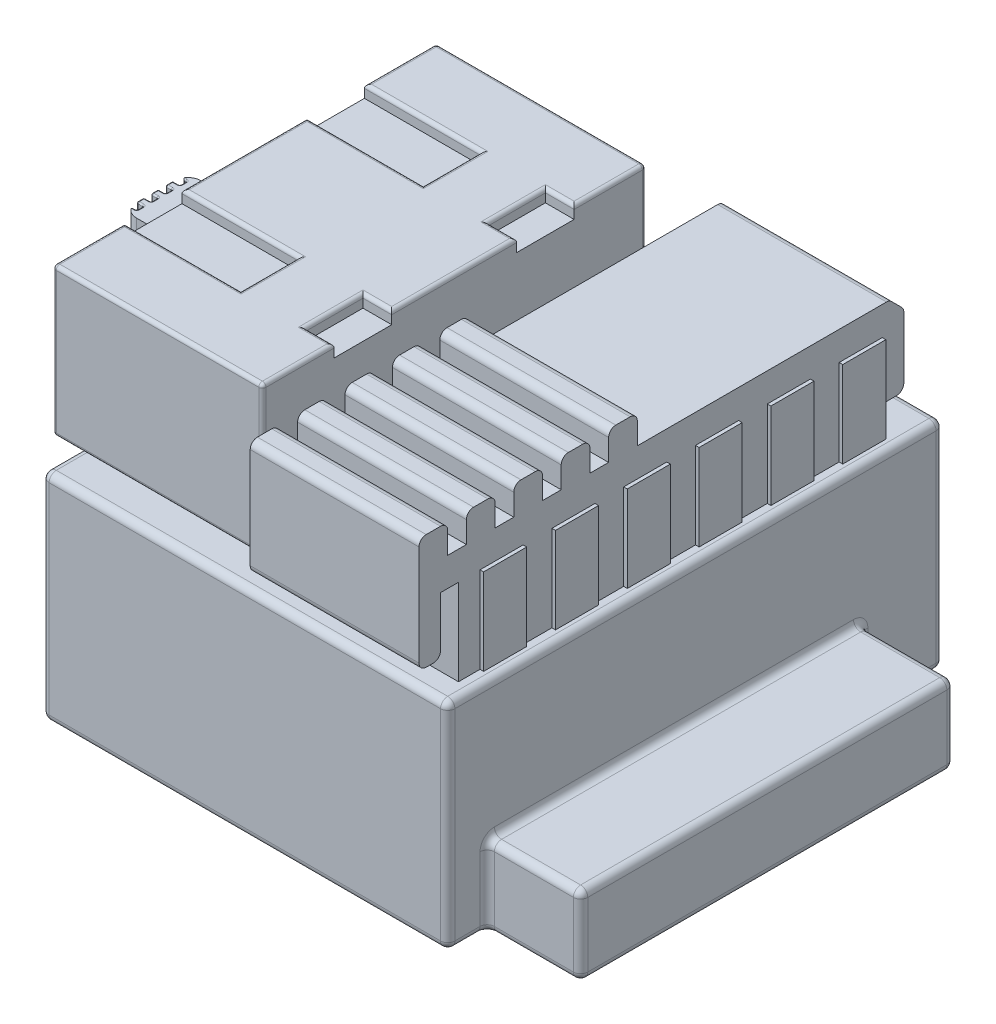
SolidWorks part; units mm, degrees
ref_plane "Front Plane" through (0, 0, 0) normal (0, 0, 1) x (1, 0, 0)
ref_plane "Top Plane" through (0, 0, 0) normal (0, 1, 0) x (1, 0, 0)
ref_plane "Right Plane" through (0, 0, 0) normal (1, 0, 0) x (0, 0, -1)
sketch "Sketch1" plane through (0, 0, 0) normal (0, 1, 0) x (1, 0, 0)
  line L1 (-14.125, -17.25) -> (14.125, -17.25)
  line L2 (-14.125, -17.25) -> (-14.125, 17.25)
  line L3 (-14.125, 17.25) -> (14.125, 17.25)
  line L4 (14.125, -17.25) -> (14.125, 17.25)
  line L5 (-14.125, -17.25) -> (14.125, 17.25) construction
  line L6 (-14.125, 17.25) -> (14.125, -17.25) construction
  line L7 (14.125, 11.5) -> (20.625, 11.5)
  line L8 (14.125, 11.5) -> (14.125, -14.5)
  line L9 (14.125, -14.5) -> (20.625, -14.5)
  line L10 (20.625, 11.5) -> (20.625, -14.5)
  point P0 (0, 0)
  dimension "D1" = 34.5
  dimension "D2" = 28.25
  dimension "D3" = 6.5
  dimension "D4" = 26
  dimension "D5" = 2.75
extrude "Boss-Extrude1" add sketch "Sketch1" along normal blind 15 contours L1 L4 L3 L2 region at (0, 0, 0)
extrude "Boss-Extrude2" add sketch "Sketch1<3>" along normal blind 5.5 contours L10 L7 L4 L9 region at (17.375, 0, 1.5)
sketch "Sketch1<3>" plane through (0, 0, 0) normal (0, 1, 0) x (1, 0, 0) same geometry as "Sketch1"
sketch "Sketch2" plane through (0, 15, 0) normal (0, 1, 0) x (1, 0, 0)
  line L0 (-14.125, -17.25) -> (-14.125, 17.25) construction
  line L1 (-12.125, -14.25) -> (-1.625, -14.25)
  line L2 (-12.125, -14.25) -> (-12.125, 10.75)
  line L3 (-12.125, 10.75) -> (-1.625, 10.75)
  line L4 (-1.625, -14.25) -> (-1.625, 10.75)
  line L5 (-14.125, -17.25) -> (14.125, -17.25) construction
  dimension "D1" = 2
  dimension "D2" = 10.5
  dimension "D3" = 25
  dimension "D4" = 3
extrude "Boss-Extrude3" add sketch "Sketch2" along normal blind 1
sketch "Sketch3" plane through (0, 16, 0) normal (0, 1, 0) x (1, 0, 0)
  line L0 (-14.125, -17.25) -> (14.125, -17.25) construction
  line L1 (-14.875, 10.95) -> (-0.275, 10.95)
  line L2 (-14.875, 10.95) -> (-14.875, -15.75)
  line L3 (-14.875, -15.75) -> (-0.275, -15.75)
  line L4 (-0.275, 10.95) -> (-0.275, -15.75)
  line L5 (-14.125, -17.25) -> (-14.125, 17.25) construction
  dimension "D1" = 1.5
  dimension "D2" = 0.75
  dimension "D3" = 14.6
  dimension "D4" = 26.7
extrude "Boss-Extrude4" add sketch "Sketch3" along normal blind 10.3
sketch "Sketch4" plane through (-14.875, 0, 0) normal (-1, 0, 0) x (0, 0, 1)
  line L0 (-10.95, 21.15) -> (15.75, 21.15) construction
  line L1 (-10.95, 26.3) -> (-10.95, 16) construction
  line L2 (15.75, 26.3) -> (15.75, 16) construction
  line L3 (-2.1, 21.15) -> (6.9, 21.15) construction
  line L4 (-2.1, 19.15) -> (6.9, 19.15)
  line L5 (-2.1, 23.15) -> (6.9, 23.15)
  line L6 (-2.1, 19.15) -> (-2.1, 23.15)
  line L7 (6.9, 19.15) -> (6.9, 23.15)
  circle A0 centre (-7.45, 21.15) radius 0.75
  circle A1 centre (12.25, 21.15) radius 0.75
  circle A2 centre (2.4, 21.15) radius 9.85 construction
  dimension "D1" = 1.5
  dimension "D2" = 3.5
  dimension "D3" = 9
  dimension "D4" = 2
  dimension "D5" = 2
extrude "Cut-Extrude1" cut sketch "Sketch4" against normal blind 2
sketch "Sketch5" plane through (-12.875, 0, 0) normal (-1, 0, 0) x (0, 0, 1)
  line L0 (-2.1, 19.15) -> (6.9, 19.15) construction
  line L1 (6.9, 23.15) -> (2.4, 23.15)
  line L2 (6.9, 23.15) -> (6.9, 19.15)
  line L3 (6.9, 19.15) -> (2.4, 19.15)
  line L4 (2.4, 23.15) -> (2.4, 19.15)
extrude "Boss-Extrude5" add sketch "Sketch5" along normal blind 6
fillet "Fillet1" radius 1 2 edges at (-18.875, 21.15, 2.4) (-18.875, 21.15, 6.9)
sketch "Sketch6" plane through (0, 23.15, 0) normal (0, 1, 0) x (1, 0, 0)
  line L0 (-18.375, -2.5383) -> (-18.375, -6.6821) construction
  line L1 (-18.875, -5.9) -> (-18.875, -3.4) construction
  line L2 (-17.875, -2.4) -> (-14.875, -2.4) construction
  line L3 (-19.375, -2.9) -> (-18.375, -2.9)
  line L4 (-19.375, -2.9) -> (-19.375, -3.4)
  line L5 (-19.375, -3.4) -> (-18.375, -3.4)
  line L6 (-18.375, -2.9) -> (-18.375, -3.4)
  line L7 (-19.375, -3.9) -> (-18.375, -3.9)
  line L8 (-19.375, -3.9) -> (-19.375, -4.4)
  line L9 (-19.375, -4.4) -> (-18.375, -4.4)
  line L10 (-18.375, -3.9) -> (-18.375, -4.4)
  line L11 (-19.375, -4.9) -> (-18.375, -4.9)
  line L12 (-19.375, -4.9) -> (-19.375, -5.4)
  line L13 (-19.375, -5.4) -> (-18.375, -5.4)
  line L14 (-18.375, -4.9) -> (-18.375, -5.4)
  line L15 (-19.375, -5.9) -> (-18.375, -5.9)
  line L16 (-19.375, -5.9) -> (-19.375, -6.4)
  line L17 (-19.375, -6.4) -> (-18.375, -6.4)
  line L18 (-18.375, -5.9) -> (-18.375, -6.4)
  line L19 (-17.875, -6.9) -> (-14.875, -6.9) construction
  line L20 (-19.375, -2.9) -> (-19.375, -6.4) construction
  dimension "D1" = 0.5
  dimension "D2" = 0.5
  dimension "D3" = 0.5
  dimension "D4" = 0.5
  dimension "D5" = 0.5
  dimension "D6" = 0.5
  dimension "D7" = 0.5
  dimension "D8" = 0.5
  dimension "D9" = 0.5
  dimension "D10" = 1
extrude "Cut-Extrude2" cut sketch "Sketch6" against normal blind 6
fillet "Fillet4" radius 0.1 46 edges at (-18.625, 19.15, 3.4) (-18.558, 19.15, 2.9) (-18.558, 23.15, 2.9) (-18.625, 23.15, 3.4) (-18.625, 19.15, 4.4) (-18.625, 19.15, 3.9) (-18.625, 23.15, 3.9) (-18.625, 23.15, 4.4) (-18.625, 19.15, 5.4) (-18.625, 19.15, 4.9) (-18.625, 23.15, 4.9) (-18.625, 23.15, 5.4) (-18.558, 19.15, 6.4) (-18.625, 19.15, 5.9) (-18.625, 23.15, 5.9) (-18.558, 23.15, 6.4) (-18.375, 19.15, 3.15) (-18.375, 21.15, 2.9) (-18.375, 23.15, 3.15) (-18.375, 21.15, 3.4) (-18.875, 21.15, 3.4) (-18.875, 23.15, 3.65) (-18.875, 21.15, 3.9) (-18.875, 19.15, 3.65) (-18.375, 19.15, 4.15) (-18.375, 21.15, 3.9) (-18.375, 23.15, 4.15) (-18.375, 21.15, 4.4) (-18.875, 21.15, 4.4) (-18.875, 23.15, 4.65) (-18.875, 21.15, 4.9) (-18.875, 19.15, 4.65) (-18.375, 19.15, 5.15) (-18.375, 21.15, 4.9) (-18.375, 23.15, 5.15) (-18.375, 21.15, 5.4) (-18.875, 21.15, 5.9) (-18.875, 19.15, 5.65) (-18.875, 21.15, 5.4) (-18.875, 23.15, 5.65) (-18.375, 19.15, 6.15) (-18.375, 21.15, 5.9) (-18.375, 23.15, 6.15) (-18.375, 21.15, 6.4) (-18.741, 21.15, 6.4) (-18.741, 21.15, 2.9)
sketch "Sketch7" plane through (0, 26.3, 0) normal (0, 1, 0) x (1, 0, 0)
  line L0 (-14.875, 10.95) -> (-14.875, -15.75) construction
  line L1 (-14.875, 5.95) -> (-6.775, 5.95)
  line L2 (-14.875, 5.95) -> (-14.875, 1.95)
  line L3 (-14.875, 1.95) -> (-6.775, 1.95)
  line L4 (-0.275, 5.95) -> (-0.275, 1.95)
  line L5 (-0.275, -15.75) -> (-0.275, 10.95) construction
  line L6 (-14.875, -15.75) -> (-0.275, -15.75) construction
  line L7 (-14.875, -6.75) -> (-6.775, -6.75)
  line L8 (-14.875, -6.75) -> (-14.875, -10.75)
  line L9 (-14.875, -10.75) -> (-6.775, -10.75)
  line L10 (-0.275, -6.75) -> (-0.275, -10.75)
  line L11 (-2.275, 5.95) -> (-0.275, 5.95)
  line L12 (-2.275, 1.95) -> (-0.275, 1.95)
  line L13 (-0.275, 10.95) -> (-14.875, 10.95) construction
  line L14 (-6.775, 10.95) -> (-6.775, -15.75) construction
  line L15 (-0.275, 10.95) -> (-14.875, 10.95) construction
  line L16 (-6.775, 5.95) -> (-6.775, 1.95)
  line L17 (-2.275, -6.75) -> (-0.275, -6.75)
  line L18 (-2.275, 5.95) -> (-2.275, 1.95)
  line L19 (-2.275, -10.75) -> (-0.275, -10.75)
  line L20 (-6.775, -6.75) -> (-6.775, -10.75)
  line L22 (-2.275, -6.75) -> (-2.275, -10.75)
  point P14 (-7.575, 10.95)
  point P21 (-0.275, -2.4)
  dimension "D1" = 5
  dimension "D2" = 4
  dimension "D3" = 5
  dimension "D4" = 4
  dimension "D5" = 6.5
  dimension "D6" = 4.5
extrude "Cut-Extrude3" cut sketch "Sketch7" against normal blind 0.85
fillet "Fillet6" radius 0.25 28 edges at (-0.275, 26.3, 13.25) (-7.575, 26.3, 15.75) (-14.875, 26.3, 13.25) (-10.825, 26.3, 10.75) (-6.775, 26.3, 8.75) (-10.825, 26.3, 6.75) (-14.875, 26.3, 2.4) (-10.825, 26.3, -1.95) (-6.775, 26.3, -3.95) (-10.825, 26.3, -5.95) (-14.875, 26.3, -8.45) (-7.575, 26.3, -10.95) (-0.275, 26.3, -8.45) (-1.275, 26.3, -5.95) (-2.275, 26.3, -3.95) (-1.275, 26.3, -1.95) (-0.275, 26.3, 2.4) (-1.275, 26.3, 6.75) (-2.275, 26.3, 8.75) (-1.275, 26.3, 10.75) (-0.275, 21.15, -10.95) (-14.875, 21.15, -10.95) (-14.875, 21.15, 15.75) (-0.275, 21.15, 15.75) (-0.275, 16, 2.4) (-7.575, 16, -10.95) (-14.875, 16, 2.4) (-7.575, 16, 15.75)
fillet "Fillet7" radius 0.5 24 edges at (20.625, 2.75, -11.5) (20.625, 0, 1.5) (20.625, 2.75, 14.5) (17.375, 5.5, 14.5) (20.625, 5.5, 1.5) (17.375, 5.5, -11.5) (14.125, 5.5, 1.5) (0, 0, -17.25) (-14.125, 0, 0) (0, 0, 17.25) (14.125, 7.5, 17.25) (14.125, 7.5, -17.25) (-14.125, 7.5, -17.25) (-14.125, 7.5, 17.25) (0, 15, -17.25) (14.125, 15, 0) (-14.125, 15, 0) (0, 15, 17.25)
sketch "Sketch8" plane through (0, 15, 0) normal (0, 1, 0) x (1, 0, 0)
  line L0 (13.375, 16.75) -> (13.375, -16.75) construction
  line L1 (13.625, 16.75) -> (-13.625, 16.75) construction
  line L2 (-13.625, -16.75) -> (13.625, -16.75) construction
  line L3 (14.125, 16.75) -> (14.125, -16.75) construction
  line L4 (13.375, 14) -> (1.125, 14)
  line L5 (13.375, 14) -> (13.375, 11)
  line L6 (13.375, 11) -> (1.125, 11)
  line L7 (1.125, 14) -> (1.125, 11)
  line L8 (13.375, 9) -> (1.125, 9)
  line L9 (13.375, 9) -> (13.375, 6)
  line L10 (13.375, 6) -> (1.125, 6)
  line L11 (1.125, 9) -> (1.125, 6)
  line L12 (13.375, 4) -> (1.125, 4)
  line L13 (13.375, 4) -> (13.375, 1)
  line L14 (13.375, 1) -> (1.125, 1)
  line L15 (1.125, 4) -> (1.125, 1)
  line L16 (13.375, -1) -> (1.125, -1)
  line L17 (13.375, -1) -> (13.375, -4)
  line L18 (13.375, -4) -> (1.125, -4)
  line L19 (1.125, -1) -> (1.125, -4)
  line L20 (13.375, -6) -> (1.125, -6)
  line L21 (13.375, -6) -> (13.375, -9)
  line L22 (13.375, -9) -> (1.125, -9)
  line L23 (1.125, -6) -> (1.125, -9)
  line L24 (13.375, -11) -> (1.125, -11)
  line L25 (13.375, -11) -> (13.375, -14)
  line L26 (13.375, -14) -> (1.125, -14)
  line L27 (1.125, -11) -> (1.125, -14)
  line L28 (-13.625, 17.25) -> (13.625, 17.25) construction
  line L29 (1.125, 14) -> (1.125, -14) construction
  dimension "D1" = 0.75
  dimension "D2" = 3
  dimension "D3" = 3
  dimension "D4" = 3
  dimension "D5" = 3
  dimension "D6" = 3
  dimension "D7" = 3
  dimension "D8" = 3.25
  dimension "D9" = 2
  dimension "D10" = 2
  dimension "D11" = 2
  dimension "D12" = 2
  dimension "D13" = 2
  dimension "D14" = 12.25
extrude "Boss-Extrude6" add sketch "Sketch8" along normal blind 6
ref_plane "Plane1" through (13.125, 0, 0) normal (1, 0, 0) x (0, 0, -1)
sketch "Sketch9" plane through (13.125, 0, 0) normal (1, 0, 0) x (0, 0, -1)
  line L0 (-14, 15) -> (-14, 21)
  line L1 (-14, 21) -> (-11, 21)
  line L2 (-11, 21) -> (-11, 15)
  line L3 (-11, 15) -> (-9, 15)
  line L4 (-9, 15) -> (-9, 21)
  line L5 (-9, 21) -> (-6, 21)
  line L6 (-6, 21) -> (-6, 15) construction
  line L7 (-9, 21) -> (-6, 21) construction
  line L8 (-6, 21) -> (-6, 15)
  line L9 (-14.25, 15) -> (10.75, 15) construction
  line L10 (-9, 15) -> (-6, 15) construction
  line L11 (-6, 15) -> (-4, 15)
  line L12 (-4, 15) -> (-4, 21)
  line L13 (-4, 21) -> (-1, 21)
  line L14 (-4, 21) -> (-1, 21) construction
  line L15 (-1, 21) -> (-1, 15)
  line L16 (-4, 15) -> (-1, 15) construction
  line L17 (-1, 21) -> (-1, 15) construction
  line L18 (-1, 15) -> (1, 15)
  line L19 (1, 15) -> (1, 21)
  line L20 (1, 21) -> (4, 21)
  line L21 (1, 21) -> (4, 21) construction
  line L22 (4, 21) -> (4, 15)
  line L23 (4, 15) -> (6, 15)
  line L24 (6, 15) -> (6, 21)
  line L25 (6, 21) -> (9, 21)
  line L26 (9, 21) -> (9, 15) construction
  line L27 (6, 21) -> (9, 21) construction
  line L28 (9, 21) -> (9, 15)
  line L29 (9, 15) -> (11, 15)
  line L30 (11, 15) -> (11, 21)
  line L31 (11, 21) -> (14, 21)
  line L32 (14, 21) -> (14, 17)
  line L33 (14, 21) -> (14, 15) construction
  line L34 (14, 17) -> (15.5, 17)
  line L35 (15.5, 17) -> (15.5, 22)
  line L36 (14.5, 23) -> (-3.05, 23)
  line L37 (-3.05, 23) -> (-3.05, 25)
  line L38 (-3.05, 25) -> (-5.05, 25)
  line L39 (-5.05, 25) -> (-5.05, 23)
  line L40 (-5.05, 23) -> (-6.35, 23)
  line L41 (-6.35, 23) -> (-6.35, 25)
  line L42 (-6.35, 25) -> (-8.35, 25)
  line L43 (-8.35, 25) -> (-8.35, 23)
  line L44 (-8.35, 23) -> (-9.65, 23)
  line L45 (-9.65, 23) -> (-9.65, 25)
  line L46 (-9.65, 25) -> (-11.65, 25)
  line L47 (-11.65, 25) -> (-11.65, 23)
  line L48 (-11.65, 23) -> (-12.95, 23)
  line L49 (-12.95, 23) -> (-12.95, 25)
  line L50 (-12.95, 25) -> (-14.95, 25)
  line L51 (-14.95, 25) -> (-14.95, 23)
  line L52 (-14.95, 23) -> (-16.25, 23)
  line L53 (-16.25, 23) -> (-16.25, 25)
  line L54 (-16.25, 25) -> (-18.25, 25)
  line L55 (-18.25, 25) -> (-18.25, 17)
  line L56 (-18.25, 17) -> (-16.75, 17)
  line L57 (-16.75, 17) -> (-16.75, 21)
  line L58 (-16.75, 21) -> (-15.5, 21)
  line L59 (-15.5, 21) -> (-15.5, 15)
  line L60 (-16.75, 15) -> (16.75, 15) construction
  line L61 (-15.5, 15) -> (-14, 15)
  line L62 (-3.05, 23) -> (-14.8492, 23) construction
  line L63 (-2.9839, 25) -> (-19.77, 25) construction
  line L64 (-14, 21) -> (-19.0557, 21) construction
  line L65 (-16.75, 17) -> (17.1356, 17) construction
  line L66 (15.5, 22) -> (14.5, 23)
  point P65 (15.5, 23)
  dimension "D1" = 2
  dimension "D2" = 2
  dimension "D3" = 1.5
  dimension "D4" = 1.5
  dimension "D5" = 1.25
  dimension "D6" = 1.5
  dimension "D7" = 8
  dimension "D8" = 2
  dimension "D9" = 1.3
  dimension "D10" = 2
  dimension "D11" = 1.3
  dimension "D12" = 2
  dimension "D13" = 1.3
  dimension "D14" = 1.3
  dimension "D15" = 2
  dimension "D16" = 2
extrude "Boss-Extrude7" add sketch "Sketch9" against normal blind 11.75
fillet "Fillet8" radius 0.5 15 edges at (7.25, 23, -14.5) (7.25, 22, -15.5) (7.25, 17, -15.5) (7.25, 25, 3.05) (7.25, 25, 5.05) (7.25, 25, 6.35) (7.25, 25, 8.35) (7.25, 25, 9.65) (7.25, 25, 11.65) (7.25, 25, 12.95) (7.25, 25, 14.95) (7.25, 25, 16.25) (7.25, 25, 18.25) (7.25, 17, 18.25) (7.25, 17, 16.75)
